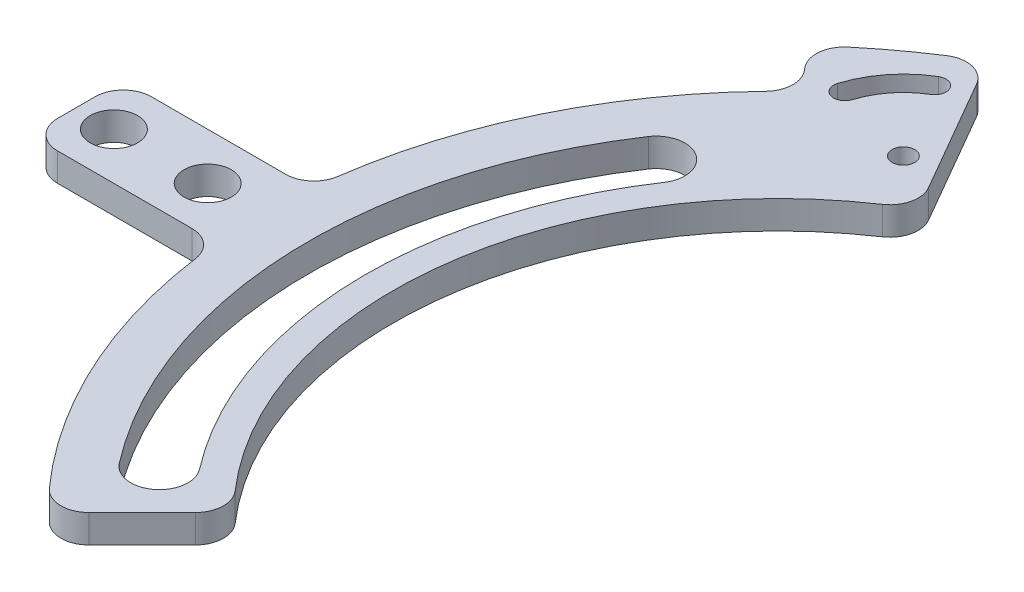
SolidWorks part; units mm, degrees
ref_plane "Front Plane" through (0, 0, 0) normal (0, 0, 1) x (1, 0, 0)
ref_plane "Top Plane" through (0, 0, 0) normal (0, 1, 0) x (1, 0, 0)
ref_plane "Right Plane" through (0, 0, 0) normal (1, 0, 0) x (0, 0, -1)
sketch "Sketch1" plane through (0, 0, 0) normal (0, 1, 0) x (1, 0, 0)
  line L0 (0, 0) -> (-47, 0) construction
  line L1 (-47, 15) -> (-47, -15) construction
  line L2 (-35, 0) -> (-35, 15) construction
  line L3 (-27.5, 47.6314) -> (-20.5, 35.507)
  line L4 (-28.9914, -28.9914) -> (-38.8909, -38.8909)
  circle A0 centre (0, 0) radius 47 construction
  arc A1 (-38.8909, -38.8909) -> (-27.5, 47.6314) centre (0, 0) cw
  arc A2 (-28.9914, -28.9914) -> (-20.5, 35.507) centre (0, 0) cw
  point P7 (-47, 0)
  dimension "D1" = 94
  dimension "D4" = 41
  dimension "D5" = 55
  dimension "D2" = 30
  dimension "D3" = 12
  dimension "D6" = 135
  dimension "D7" = 120
extrude "Boss-Extrude1" add sketch "Sketch1" along normal blind 3
sketch "Sketch2" plane through (0, 3, 0) normal (0, 1, 0) x (1, 0, 0)
  line L0 (-20.5, 35.507) -> (-27.5, 47.6314) construction
  line L1 (-38.8909, -38.8909) -> (-28.9914, -28.9914) construction
  arc A0 (-35.2876, -31.0449) -> (-37.2968, 28.5999) centre (0, 0) cw
  dimension "D1" = 47
  dimension "D2" = 18
  dimension "D3" = 3
extrude "Cut-Extrude-Thin1" cut sketch "Sketch2" against normal blind 3 and the other way through all thin thin type mid plane wall 6.1
fillet "Fillet1" radius 3.05 4 edges at (-39.7171, 1.5, -30.4558) (-34.8764, 1.5, -26.7439) (-32.9976, 1.5, 29.0303) (-37.5775, 1.5, 33.0595)
sketch "Sketch3" plane through (0, 0, 0) normal (0, 1, 0) x (1, 0, 0)
  line L0 (-27.5, 47.6314) -> (-30.5, 52.8275)
  line L1 (-41.6019, 44.6126) -> (-37.5099, 40.2245)
  line L2 (-20.5, 35.507) -> (-27.5, 47.6314) construction
  arc A0 (-30.5, 52.8275) -> (-41.6019, 44.6126) centre (0, 0) ccw
  arc A1 (-27.5, 47.6314) -> (-38.8909, -38.8909) centre (0, 0) ccw construction
  arc A2 (-37.5099, 40.2245) -> (-27.5, 47.6314) centre (0, 0) cw
  dimension "D2" = 13
  dimension "D1" = 20
extrude "Boss-Extrude2" add sketch "Sketch3" along normal up to surface (3 mm away) up to face at (-40.216, 3, 1.3547)
sketch "Sketch4" plane through (0, 3, 0) normal (0, 1, 0) x (1, 0, 0)
  line L0 (0, 0) -> (-33.6682, 50.867) construction
  line L1 (-20.5, 35.507) -> (-30.5, 52.8275) construction
  arc A0 (-30.5, 52.8275) -> (-41.6019, 44.6126) centre (0, 0) ccw construction
  circle A1 centre (-26.217, 39.6096) radius 1.2
  arc A3 (-20.5, 35.507) -> (-28.9914, -28.9914) centre (0, 0) ccw construction
  dimension "D1" = 2.4
  dimension "D3" = 47.5
  dimension "D4" = 3.5
extrude "Cut-Extrude1" cut sketch "Sketch4" against normal through all both and the other way through all
sketch "Sketch5" plane through (0, 3, 0) normal (0, 1, 0) x (1, 0, 0)
  line L0 (-20.5, 35.507) -> (-30.5, 52.8275) construction
  arc A0 (-29.9826, 48.3314) -> (-35.5698, 41.2757) centre (-26.217, 39.6096) ccw
  dimension "D1" = 9.5
  dimension "D2" = 9
  dimension "D3" = 1.8
extrude "Cut-Extrude-Thin2" cut sketch "Sketch5" against normal blind 3 and the other way through all thin thin type mid plane wall 2.4
fillet "Fillet2" radius 1.2 4 edges at (-34.3884, 1.5, -41.0652) (-36.7512, 1.5, -41.4861) (-30.4583, 1.5, -49.4331) (-29.507, 1.5, -47.2297)
sketch "Sketch6" plane through (0, 0, 0) normal (0, 1, 0) x (1, 0, 0)
  line L0 (0, 0) -> (-64.7723, 0) construction
  line L2 (-74.7723, -5) -> (-54.7723, -5)
  line L3 (-74.7723, -5) -> (-74.7723, 5)
  line L4 (-74.7723, 5) -> (-54.7723, 5)
  line L5 (-54.7723, -5) -> (-54.7723, 5)
  line L6 (-64.7723, 5) -> (-64.7723, -5) construction
  line L7 (-74.7723, 0) -> (-54.7723, 0) construction
  arc A0 (-37.5099, 40.2245) -> (-38.8909, -38.8909) centre (0, 0) ccw construction
  circle A1 centre (-70.7723, 0) radius 2.525
  circle A2 centre (-60.7723, 0) radius 2.525
  dimension "D3" = 5.05
  dimension "D4" = 10
  dimension "D5" = 4
  dimension "D1" = 20
  dimension "D2" = 10
extrude "Boss-Extrude3" add sketch "Sketch6" along normal up to surface (3 mm away) up to face at (-33.1495, 3, -45.0991)
fillet "Fillet3" radius 3 10 edges at (-74.7723, 1.5, 5) (-74.7723, 1.5, -5) (-54.7723, 1.5, 5) (-54.7723, 1.5, -5) (-37.5099, 1.5, -40.2245) (-41.6019, 1.5, -44.6126) (-30.5, 1.5, -52.8275) (-20.5, 1.5, -35.507) (-28.9914, 1.5, 28.9914) (-38.8909, 1.5, 38.8909)
